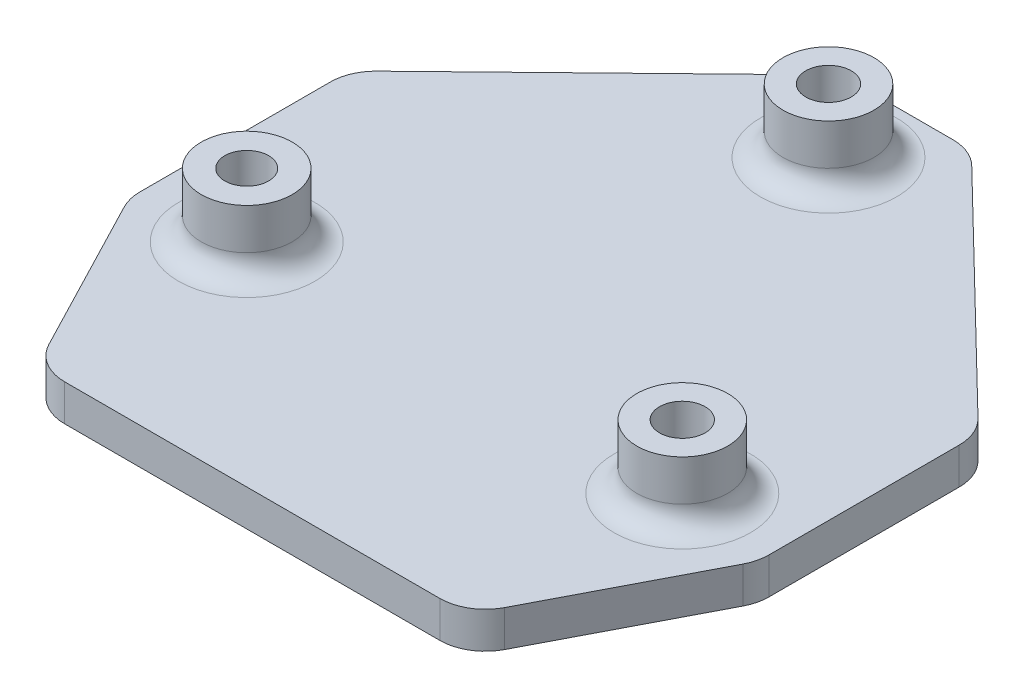
SolidWorks part; units mm, degrees
material "ABS"
ref_plane "Front Plane" through (0, 0, 0) normal (0, 0, 1) x (1, 0, 0)
ref_plane "Top Plane" through (0, 0, 0) normal (0, 1, 0) x (1, 0, 0)
ref_plane "Right Plane" through (0, 0, 0) normal (1, 0, 0) x (0, 0, -1)
sketch "Sketch1" plane through (0, 0, 0) normal (0, 1, 0) x (1, 0, 0)
  line L0 (-2.9978, 1.6275) -> (-2.9978, -22.6068)
  line L1 (-2.9978, -22.6068) -> (7.9116, -43.613)
  line L2 (7.9116, -43.613) -> (31.5573, -43.613)
  line L3 (31.5573, -47.7519) -> (31.5573, 17.1115) construction
  line L4 (24.3856, 28.2372) -> (-2.9978, 1.6275)
  line L5 (55.2031, -43.613) -> (31.5573, -43.613)
  line L6 (66.1125, -22.6068) -> (55.2031, -43.613)
  line L7 (66.1125, 1.6275) -> (66.1125, -22.6068)
  line L8 (38.729, 28.2372) -> (66.1125, 1.6275)
  line L9 (-2.9978, 7.2109) -> (66.1125, 7.2109) construction
  line L10 (66.1125, -7.7891) -> (-2.9978, -7.7891) construction
  line L11 (24.3856, 28.2372) -> (38.729, 28.2372)
  line L12 (55.4901, -20.2891) -> (7.6245, -20.2891) construction
  circle A1 centre (55.4901, -20.2891) radius 2.5
  circle A2 centre (31.5573, 19.7109) radius 2.5
  circle A3 centre (7.6245, -20.2891) radius 2.5
  circle A4 centre (31.5573, 19.7109) radius 12.5 construction
  circle A5 centre (7.6245, -20.2891) radius 12.5 construction
  point P6 (31.5573, 35.2062)
  point P22 (31.5573, -20.2891)
  dimension "D1" = 5
  dimension "D2" = 5
  dimension "D3" = 25
  dimension "D4" = 25
  dimension "D5" = 15
extrude "Boss-Extrude2" add sketch "Sketch1" along normal blind 4
fillet "Fillet1" radius 5 8 edges at (7.9116, 2, 43.613) (55.2031, 2, 43.613) (66.1125, 2, 22.6068) (66.1125, 2, -1.6275) (-2.9978, 2, -1.6275) (-2.9978, 2, 22.6068) (24.3856, 2, -28.2372) (38.729, 2, -28.2372)
sketch "Sketch2" plane through (0, 4, 0) normal (0, 1, 0) x (1, 0, 0)
  circle A0 centre (31.5573, 19.7109) radius 5
  circle A1 centre (31.5573, 19.7109) radius 2.5
  circle A2 centre (55.4901, -20.2891) radius 2.5
  circle A3 centre (55.4901, -20.2891) radius 5
  circle A4 centre (7.6245, -20.2891) radius 2.4106
  circle A5 centre (7.6245, -20.2891) radius 5
  dimension "D1" = 10
  dimension "7.5" = 10
  dimension "D2" = 10
extrude "Boss-Extrude3" add sketch "Sketch2" along normal blind 7
fillet "Fillet2" radius 2.5 3 edges at (55.4901, 4, 25.2891) (7.6245, 4, 25.2891) (31.5573, 4, -14.7109)
